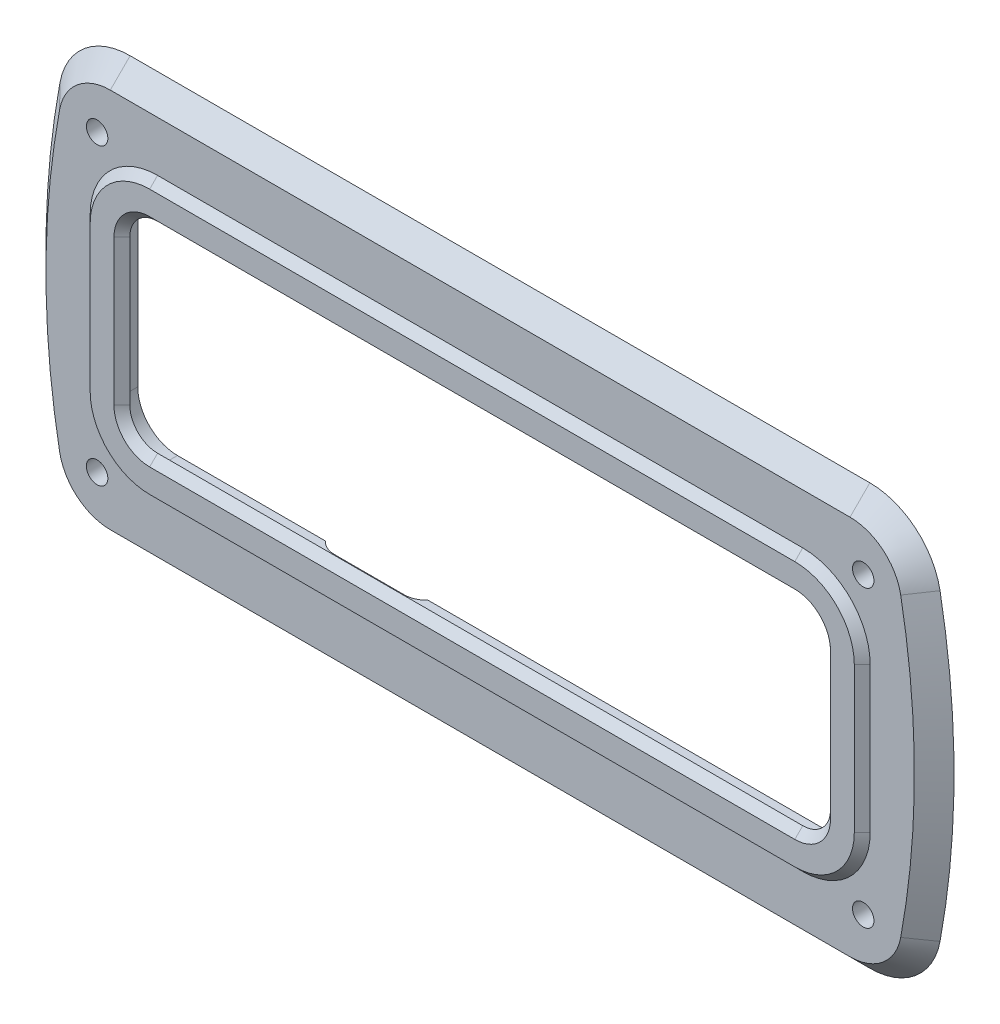
SolidWorks part; units mm, degrees
material "PLA"
ref_plane "Front Plane" through (0, 0, 0) normal (0, 0, 1) x (1, 0, 0)
ref_plane "Top Plane" through (0, 0, 0) normal (0, 1, 0) x (1, 0, 0)
ref_plane "Right Plane" through (0, 0, 0) normal (1, 0, 0) x (0, 0, -1)
sketch "Sketch1" plane through (0, 0, 0) normal (0, 0, 1) x (1, 0, 0)
  line L0 (-46.267, -27.3056) -> (46.983, -27.3056)
  line L1 (46.983, 25.6944) -> (-46.267, 25.6944)
  line L2 (-40.307, -14.9706) -> (41.023, -14.9706)
  line L3 (46.023, -9.9706) -> (46.023, 8.3594)
  line L4 (41.023, 13.3594) -> (-40.307, 13.3594)
  line L5 (-45.307, 8.3594) -> (-45.307, -9.9706)
  line L6 (-52.02, -25.2268) -> (-43.8425, -13.5061) construction
  line L7 (-43.8425, 11.895) -> (-52.02, 23.6156) construction
  line L8 (44.5586, 11.895) -> (52.736, 23.6156) construction
  line L9 (44.5586, -13.5061) -> (52.736, -25.2268) construction
  arc A0 (-55.1153, -19.9507) -> (-46.267, -27.3056) centre (-46.267, -18.3056) ccw
  arc A1 (46.983, -27.3056) -> (55.8314, -19.9507) centre (46.983, -18.3056) ccw
  arc A2 (55.8314, -19.9507) -> (55.8314, 18.3395) centre (-47.142, -0.8056) ccw
  arc A3 (55.8314, 18.3395) -> (46.983, 25.6944) centre (46.983, 16.6944) ccw
  arc A4 (-46.267, 25.6944) -> (-55.1153, 18.3395) centre (-46.267, 16.6944) ccw
  arc A5 (-55.1153, 18.3395) -> (-55.1153, -19.9507) centre (47.858, -0.8056) ccw
  circle A6 centre (48.6473, -19.3664) radius 1.35
  circle A7 centre (48.6473, 17.7553) radius 1.35
  circle A8 centre (-47.9312, 17.7553) radius 1.35
  arc A10 (-45.307, -9.9706) -> (-40.307, -14.9706) centre (-40.307, -9.9706) ccw
  arc A11 (41.023, -14.9706) -> (46.023, -9.9706) centre (41.023, -9.9706) ccw
  arc A12 (46.023, 8.3594) -> (41.023, 13.3594) centre (41.023, 8.3594) ccw
  arc A13 (-40.307, 13.3594) -> (-45.307, 8.3594) centre (-40.307, 8.3594) ccw
  circle A14 centre (-47.9312, -19.3664) radius 1.3539
  point P43 (48.6473, -19.3664)
  point P45 (-47.9312, 17.7553)
  point P46 (48.6473, 17.7553)
extrude "Boss-Extrude1" add sketch "Sketch1" along normal blind 2.5
sketch "Sketch2" plane through (0, 0, 2.5) normal (0, 0, 1) x (1, 0, 0)
  line L24 (49.523, -9.9706) -> (49.523, 8.3594)
  line L25 (-40.307, -18.4706) -> (41.023, -18.4706)
  line L26 (-48.807, 8.3594) -> (-48.807, -9.9706)
  line L27 (41.023, 16.8594) -> (-40.307, 16.8594)
  line L28 (49.523, -9.9706) -> (49.523, 8.3594)
  line L29 (-40.307, -18.4706) -> (41.023, -18.4706)
  line L30 (-48.807, 8.3594) -> (-48.807, -9.9706)
  line L31 (41.023, 16.8594) -> (-40.307, 16.8594)
  line L34 (41.023, 11.8594) -> (-40.307, 11.8594)
  line L35 (-43.807, 8.3594) -> (-43.807, -9.9706)
  line L36 (-40.307, -13.4706) -> (41.023, -13.4706)
  line L37 (44.523, -9.9706) -> (44.523, 8.3594)
  arc A20 (49.523, 8.3594) -> (41.023, 16.8594) centre (41.023, 8.3594) ccw
  arc A21 (41.023, -18.4706) -> (49.523, -9.9706) centre (41.023, -9.9706) ccw
  arc A22 (-48.807, -9.9706) -> (-40.307, -18.4706) centre (-40.307, -9.9706) ccw
  arc A23 (-40.307, 16.8594) -> (-48.807, 8.3594) centre (-40.307, 8.3594) ccw
  arc A24 (49.523, 8.3594) -> (41.023, 16.8594) centre (41.023, 8.3594) ccw
  arc A25 (41.023, -18.4706) -> (49.523, -9.9706) centre (41.023, -9.9706) ccw
  arc A26 (-48.807, -9.9706) -> (-40.307, -18.4706) centre (-40.307, -9.9706) ccw
  arc A27 (-40.307, 16.8594) -> (-48.807, 8.3594) centre (-40.307, 8.3594) ccw
  arc A33 (44.523, 8.3594) -> (41.023, 11.8594) centre (41.023, 8.3594) ccw
  arc A34 (-40.307, 11.8594) -> (-43.807, 8.3594) centre (-40.307, 8.3594) ccw
  arc A35 (-43.807, -9.9706) -> (-40.307, -13.4706) centre (-40.307, -9.9706) ccw
  arc A36 (41.023, -13.4706) -> (44.523, -9.9706) centre (41.023, -9.9706) ccw
  dimension "D1" = 3.5
  dimension "D2" = 5
extrude "Boss-Extrude2" add sketch "Sketch2" along normal blind 1
chamfer "Chamfer1" distance 1 angle 45 16 edges at (-42.7818, 10.8343, 3.5) (-43.807, -0.8056, 3.5) (-42.7818, -12.4454, 3.5) (0.358, -13.4706, 3.5) (43.4979, -12.4454, 3.5) (44.523, -0.8056, 3.5) (43.4979, 10.8343, 3.5) (0.358, 11.8594, 3.5) (49.523, -0.8056, 3.5) (47.0334, -15.981, 3.5) (0.358, -18.4706, 3.5) (-46.3174, -15.981, 3.5) (-48.807, -0.8056, 3.5) (-46.3174, 14.3698, 3.5) (0.358, 16.8594, 3.5) (47.0334, 14.3698, 3.5)
chamfer "Chamfer2" distance 2.5 angle 45 8 edges at (0.358, -27.3056, 2.5) (52.736, -25.2268, 2.5) (-52.02, -25.2268, 2.5) (57.596, -0.8056, 2.5) (-56.88, -0.8056, 2.5) (52.736, 23.6156, 2.5) (-52.02, 23.6156, 2.5) (0.358, 25.6944, 2.5)
ref_plane "Plane1" through (-46.267, -27.3056, 0) normal (1, 0, 0) x (0, 0, -1)
sketch "Sketch5" plane through (0, 0, 0) normal (0, 1, 0) x (1, 0, 0)
  line L8 (-22.3928, 4.5905) -> (-22.3928, 1.8904)
  line L9 (-10.7928, 7.3905) -> (-19.5929, 7.3905)
  line L10 (-7.9928, 1.8905) -> (-7.9928, 4.5905)
  line L11 (-19.5928, -0.9095) -> (-10.7928, -0.9095)
  line L12 (-22.3928, 4.5905) -> (-22.3928, 1.8904)
  line L13 (-10.7928, 7.3905) -> (-19.5929, 7.3905)
  line L14 (-7.9928, 1.8905) -> (-7.9928, 4.5905)
  line L15 (-19.5928, -0.9095) -> (-10.7928, -0.9095)
  spline S8 degree 3 poles (3912.111, 717.9641) (591.0864, 166.3811) (-29.0634, 35.0879) (-22.3033, 1.1648) (-22.2493, 0.9865) (-22.1091, 0.6487) (-22.023, 0.4881) (-21.8194, 0.1831) (-21.7017, 0.0395) (-21.4436, -0.218) (-21.3028, -0.3343) (-20.996, -0.54) (-20.8345, -0.6256) (-20.4982, -0.7657) (-20.321, -0.8195) (6.4052, -6.1271) (80.1312, 366.7635) (555.2461, 3956.8945) knots -23.396455 -23.396455 -23.396455 -23.396455 0.125 0.125 0.25 0.25 0.375 0.375 0.5 0.5 0.625 0.625 0.75 0.75 0.875 0.875 19.270679 19.270679 19.270679 19.270679 only from (-22.3928, 1.8904) to (-19.5928, -0.9095)
  spline S9 degree 3 poles (696.46, -3927.1647) (144.8592, -605.9158) (13.6001, 14.0602) (-20.3185, 7.301) (-20.4967, 7.2469) (-20.8346, 7.1068) (-20.9952, 7.0207) (-21.3002, 6.8171) (-21.4438, 6.6993) (-21.7013, 6.4413) (-21.8176, 6.3005) (-22.0233, 5.9936) (-22.1088, 5.8321) (-22.249, 5.4958) (-22.3028, 5.3186) (-27.6104, -21.4075) (345.2812, -95.1365) (3935.3456, -570.2705) knots -23.393333 -23.393333 -23.393333 -23.393333 0.125 0.125 0.25 0.25 0.375 0.375 0.5 0.5 0.625 0.625 0.75 0.75 0.875 0.875 19.270631 19.270631 19.270631 19.270631 only from (-19.5929, 7.3905) to (-22.3928, 4.5905)
  spline S10 degree 3 poles (-3942.5248, -711.4863) (-621.4703, -159.8996) (-1.3222, -28.6069) (-8.0823, 5.3161) (-8.1363, 5.4944) (-8.2765, 5.8323) (-8.3626, 5.9929) (-8.5662, 6.2979) (-8.684, 6.4415) (-8.942, 6.699) (-9.0828, 6.8152) (-9.3896, 7.0209) (-9.5511, 7.1065) (-9.8875, 7.2467) (-10.0646, 7.3005) (-36.7922, 12.6083) (-110.5244, -360.3204) (-585.6149, -3950.2382) knots -23.396424 -23.396424 -23.396424 -23.396424 0.125 0.125 0.25 0.25 0.375 0.375 0.5 0.5 0.625 0.625 0.75 0.75 0.875 0.875 19.271596 19.271596 19.271596 19.271596 only from (-7.9928, 4.5905) to (-10.7928, 7.3905)
  spline S11 degree 3 poles (-726.8283, 3933.6243) (-175.2105, 612.2349) (-43.9813, -7.5783) (-10.0672, -0.82) (-9.8889, -0.766) (-9.551, -0.6259) (-9.3904, -0.5398) (-9.0854, -0.3361) (-8.9418, -0.2184) (-8.6843, 0.0397) (-8.5681, 0.1805) (-8.3623, 0.4873) (-8.2768, 0.6488) (-8.1366, 0.9851) (-8.0828, 1.1623) (-2.7753, 27.8883) (-375.6617, 101.6166) (-3965.6631, 576.7442) knots -23.390263 -23.390263 -23.390263 -23.390263 0.125 0.125 0.25 0.25 0.375 0.375 0.5 0.5 0.625 0.625 0.75 0.75 0.875 0.875 19.270505 19.270505 19.270505 19.270505 only from (-10.7928, -0.9095) to (-7.9928, 1.8905)
  spline S12 degree 3 poles (-22.3928, 1.8904) (-22.3928, 1.7055) (-22.3748, 1.5235) (-22.3033, 1.1648) (-22.2493, 0.9865) (-22.1091, 0.6487) (-22.023, 0.4881) (-21.8194, 0.1831) (-21.7017, 0.0395) (-21.4436, -0.218) (-21.3028, -0.3343) (-20.996, -0.54) (-20.8345, -0.6256) (-20.4982, -0.7657) (-20.321, -0.8195) (-19.9602, -0.8912) (-19.7777, -0.9095) (-19.5928, -0.9095) knots 0 0 0 0 0.125 0.125 0.25 0.25 0.375 0.375 0.5 0.5 0.625 0.625 0.75 0.75 0.875 0.875 1 1 1 1
  spline S13 degree 3 poles (-19.5929, 7.3905) (-19.7777, 7.3905) (-19.9598, 7.3724) (-20.3185, 7.301) (-20.4967, 7.2469) (-20.8346, 7.1068) (-20.9952, 7.0207) (-21.3002, 6.8171) (-21.4438, 6.6993) (-21.7013, 6.4413) (-21.8176, 6.3005) (-22.0233, 5.9936) (-22.1088, 5.8321) (-22.249, 5.4958) (-22.3028, 5.3186) (-22.3744, 4.9579) (-22.3928, 4.7753) (-22.3928, 4.5905) knots 0 0 0 0 0.125 0.125 0.25 0.25 0.375 0.375 0.5 0.5 0.625 0.625 0.75 0.75 0.875 0.875 1 1 1 1
  spline S14 degree 3 poles (-7.9928, 4.5905) (-7.9928, 4.7754) (-8.0109, 4.9575) (-8.0823, 5.3161) (-8.1363, 5.4944) (-8.2765, 5.8323) (-8.3626, 5.9929) (-8.5662, 6.2979) (-8.684, 6.4415) (-8.942, 6.699) (-9.0828, 6.8152) (-9.3896, 7.0209) (-9.5511, 7.1065) (-9.8875, 7.2467) (-10.0646, 7.3005) (-10.4254, 7.3721) (-10.608, 7.3905) (-10.7928, 7.3905) knots 0 0 0 0 0.125 0.125 0.25 0.25 0.375 0.375 0.5 0.5 0.625 0.625 0.75 0.75 0.875 0.875 1 1 1 1
  spline S15 degree 3 poles (-10.7928, -0.9095) (-10.6079, -0.9095) (-10.4258, -0.8915) (-10.0672, -0.82) (-9.8889, -0.766) (-9.551, -0.6259) (-9.3904, -0.5398) (-9.0854, -0.3361) (-8.9418, -0.2184) (-8.6843, 0.0397) (-8.5681, 0.1805) (-8.3623, 0.4873) (-8.2768, 0.6488) (-8.1366, 0.9851) (-8.0828, 1.1623) (-8.0112, 1.5231) (-7.9928, 1.7056) (-7.9928, 1.8905) knots 0 0 0 0 0.125 0.125 0.25 0.25 0.375 0.375 0.5 0.5 0.625 0.625 0.75 0.75 0.875 0.875 1 1 1 1
  dimension "D1" = 0.5
extrude "Cut-Extrude1" cut sketch "Sketch5" against normal up to surface (28.3056 mm away) contours L15 S15 L14 S14 L13 S13 L12 S12 region at (-22.2994, 0, -3.2474) region at (-20.8978, 0, -5.8506) region at (-20.763, 0, -0.6182) region at (-18.9185, 0, -7.3461) region at (-18.9663, 0, -3.1707) region at (-18.4227, 0, 0.7815) region at (-18.4418, 0, -7.3055) region at (-18.5381, 0, -7.1534) region at (-16.6669, 0, -5.0884) region at (-17.969, 0, 0.5124) region at (-17.8504, 0, 0.8175) region at (-15.2108, 0, -6.4329) region at (-16.4442, 0, -1.432) region at (-15.1928, 0, -3.2405) region at (-15.1748, 0, -0.0481) region at (-12.5353, 0, -7.2984) region at (-13.9415, 0, -5.0489) region at (-13.7187, 0, -1.3926) region at (-11.9437, 0, 0.8246) region at (-11.963, 0, -7.2625) region at (-12.4168, 0, -6.9933) region at (-11.4193, 0, -3.3103) region at (-11.8474, 0, 0.6724) region at (-11.467, 0, 0.8652) region at (-9.6227, 0, -5.8628) region at (-9.4879, 0, -0.6304) region at (-8.0862, 0, -3.2335)
